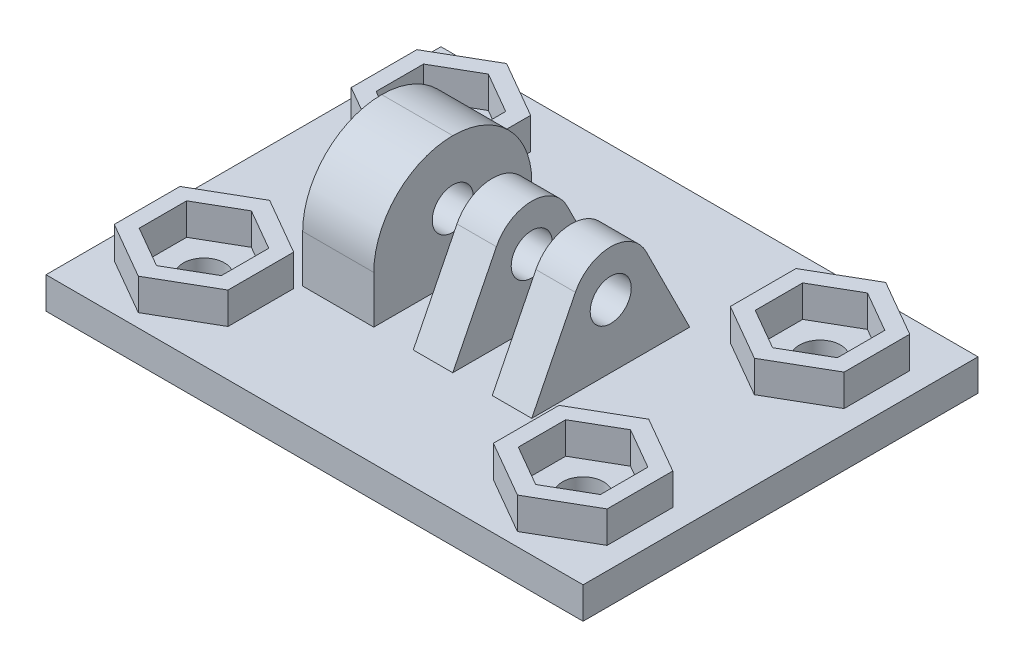
SolidWorks part; units mm, degrees
ref_plane "Front Plane" through (0, 0, 0) normal (0, 0, 1) x (1, 0, 0)
ref_plane "Top Plane" through (0, 0, 0) normal (0, 1, 0) x (1, 0, 0)
ref_plane "Right Plane" through (0, 0, 0) normal (1, 0, 0) x (0, 0, -1)
sketch "Sketch1" plane through (0, 0, 0) normal (0, 1, 0) x (1, 0, 0)
  line L0 (-21.59, 0) -> (-21.59, 31.75)
  line L1 (-21.59, 31.75) -> (21.59, 31.75)
  line L2 (-15.24, 25.4) -> (15.24, 25.4) construction
  line L3 (-15.24, 6.35) -> (15.24, 6.35) construction
  line L6 (21.59, 31.75) -> (21.59, 0)
  line L7 (21.59, 0) -> (-21.59, 0)
  line L8 (-15.24, 31.75) -> (-15.24, 0) construction
  line L9 (15.24, 31.75) -> (15.24, 0) construction
  circle A0 centre (-15.24, 25.4) radius 1.651
  circle A1 centre (-15.24, 6.35) radius 1.651
  circle A2 centre (15.24, 25.4) radius 1.651
  circle A3 centre (15.24, 6.35) radius 1.651
  dimension "D2" = 6.35
  dimension "D4" = 3.302
  dimension "D1" = 6.35
  dimension "D3" = 43.18
  dimension "D5" = 31.75
  dimension "D6" = 6.35
  dimension "D7" = 6.35
extrude "Boss-Extrude1" add sketch "Sketch1" along normal blind 2.54
sketch "Sketch2" plane through (0, 0, 0) normal (1, 0, 0) x (0, 0, -1)
  line L0 (22.225, 2.54) -> (15.875, 15.24)
  line L1 (0, 2.54) -> (31.75, 2.54) construction
  line L2 (15.875, 15.24) -> (9.525, 2.54)
  line L3 (22.225, 2.54) -> (9.525, 2.54)
  line L4 (15.875, 2.54) -> (15.875, 0) construction
  line L5 (0, 2.54) -> (31.75, 2.54) construction
  line L6 (0, 0) -> (31.75, 0) construction
  circle A0 centre (15.875, 7.62) radius 1.651
  dimension "D2" = 3.302
  dimension "D1" = 12.7
  dimension "D3" = 12.7
  dimension "D4" = 5.08
extrude "Boss-Extrude2" add sketch "Sketch2" along normal mid plane 15.875 contours L3 L0 L2 | A0
sketch "Sketch3" plane through (0, 2.54, 0) normal (0, 1, 0) x (1, 0, 0)
  line L1 (7.9375, 22.225) -> (-7.9375, 22.225) construction
  line L2 (-4.7625, 22.225) -> (-1.5875, 22.225)
  line L3 (-4.7625, 22.225) -> (-4.7625, 9.525)
  line L4 (-4.7625, 9.525) -> (-1.5875, 9.525)
  line L6 (-1.5875, 22.225) -> (-1.5875, 9.525)
  line L8 (7.9375, 9.525) -> (-7.9375, 9.525) construction
  line L9 (1.5875, 22.225) -> (4.7625, 22.225)
  line L10 (1.5875, 22.225) -> (1.5875, 9.525)
  line L11 (1.5875, 9.525) -> (4.7625, 9.525)
  line L12 (4.7625, 22.225) -> (4.7625, 9.525)
  line L13 (-1.5875, 9.525) -> (1.5875, 9.525) construction
  line L14 (0, 9.525) -> (0, 0) construction
  line L15 (-21.59, 0) -> (21.59, 0) construction
  dimension "D1" = 3.175
  dimension "D2" = 3.175
extrude "Cut-Extrude1" cut sketch "Sketch3" along normal up to vertex (12.7 mm away) up to point (7.9375, 15.24, -15.875)
fillet "Fillet1" radius 3.175 3 edges at (6.35, 15.24, -15.875) (0, 15.24, -15.875) (-6.35, 15.24, -15.875)
sketch "Sketch6" plane through (-7.9375, 0, 0) normal (-1, 0, 0) x (0, 0, 1)
  line L1 (-9.525, 2.54) -> (-22.225, 2.54)
  line L2 (-9.525, 2.54) -> (-9.525, 12.7)
  line L3 (-9.525, 12.7) -> (-22.225, 12.7)
  line L4 (-22.225, 2.54) -> (-22.225, 12.7)
  circle A0 centre (-15.875, 7.62) radius 1.651
  circle A1 centre (-15.875, 7.62) radius 1.651 construction
  dimension "D1" = 10.16
extrude "Boss-Extrude5" add sketch "Sketch6" against normal up to surface (3.175 mm away) up to face at (-4.7625, 7.62, -17.526)
sketch "Sketch4" plane through (-7.9375, 0, 0) normal (-1, 0, 0) x (0, 0, 1)
  line L0 (-22.225, 12.7) -> (-22.225, 2.54) construction
  line L1 (-22.225, 2.54) -> (-9.525, 2.54)
  line L2 (-22.225, 2.54) -> (-22.225, 12.7)
  line L3 (-22.225, 12.7) -> (-9.525, 12.7)
  line L4 (-9.525, 2.54) -> (-9.525, 12.7)
  line L5 (-15.875, 3.8072) -> (-12.573, 5.7136)
  line L6 (-12.573, 5.7136) -> (-12.573, 9.5264)
  line L7 (-12.573, 9.5264) -> (-15.875, 11.4328)
  line L8 (-15.875, 11.4328) -> (-19.177, 9.5264)
  line L9 (-19.177, 9.5264) -> (-19.177, 5.7136)
  line L10 (-19.177, 5.7136) -> (-15.875, 3.8072)
  line L11 (-22.225, 2.54) -> (-9.525, 2.54) construction
  circle A0 centre (-15.875, 7.62) radius 3.302 construction
  circle A1 centre (-15.875, 7.62) radius 1.651 construction
  circle A2 centre (-15.875, 7.62) radius 1.651
  point P5 (0, 0)
  point P8 (-22.225, 2.54)
  point P23 (0, 0)
  point P24 (0, 0)
  point P25 (-9.525, 2.54)
  line M7 (-22.225, 2.54) -> (-9.525, 2.54)
  line M24 (-9.525, 2.54) -> (-9.525, 12.7)
  line M25 (-9.525, 12.7) -> (-22.225, 12.7)
  line M26 (-22.225, 12.7) -> (-22.225, 2.54)
  dimension "D1" = 10.16
  dimension "D2" = 6.604
extrude "Boss-Extrude6" add sketch "Sketch4" along normal blind 2.54 contours L10 L9 L8 L7 L6 L5 M26 M7 M24 M25 region at (-7.9375, 7.62, -22.0624)
fillet "Fillet2" radius 6.35 2 edges at (-7.62, 12.7, -9.525) (-7.62, 12.7, -22.225)
sketch "Sketch7" plane through (0, 2.54, 0) normal (0, 1, 0) x (1, 0, 0)
  line L1 (-15.24, 30.6793) -> (-19.812, 28.0396)
  line L2 (-19.812, 28.0396) -> (-19.812, 22.7604)
  line L3 (-19.812, 22.7604) -> (-15.24, 20.1207)
  line L4 (-15.24, 20.1207) -> (-10.668, 22.7604)
  line L5 (-10.668, 22.7604) -> (-10.668, 28.0396)
  line L6 (-10.668, 28.0396) -> (-15.24, 30.6793)
  line L7 (15.24, 29.2128) -> (11.938, 27.3064)
  line L8 (11.938, 27.3064) -> (11.938, 23.4936)
  line L9 (11.938, 23.4936) -> (15.24, 21.5872)
  line L10 (15.24, 21.5872) -> (18.542, 23.4936)
  line L11 (18.542, 23.4936) -> (18.542, 27.3064)
  line L12 (18.542, 27.3064) -> (15.24, 29.2128)
  line L13 (15.24, 30.6793) -> (10.668, 28.0396)
  line L14 (10.668, 28.0396) -> (10.668, 22.7604)
  line L15 (10.668, 22.7604) -> (15.24, 20.1207)
  line L16 (15.24, 20.1207) -> (19.812, 22.7604)
  line L17 (-15.24, 29.2128) -> (-18.542, 27.3064)
  line L18 (-18.542, 27.3064) -> (-18.542, 23.4936)
  line L19 (-18.542, 23.4936) -> (-15.24, 21.5872)
  line L20 (-15.24, 21.5872) -> (-11.938, 23.4936)
  line L21 (-11.938, 23.4936) -> (-11.938, 27.3064)
  line L22 (-11.938, 27.3064) -> (-15.24, 29.2128)
  line L23 (19.812, 22.7604) -> (19.812, 28.0396)
  line L24 (19.812, 28.0396) -> (15.24, 30.6793)
  line L25 (15.24, 10.1628) -> (11.938, 8.2564)
  line L26 (11.938, 8.2564) -> (11.938, 4.4436)
  line L27 (11.938, 4.4436) -> (15.24, 2.5372)
  line L28 (15.24, 2.5372) -> (18.542, 4.4436)
  line L29 (18.542, 4.4436) -> (18.542, 8.2564)
  line L30 (18.542, 8.2564) -> (15.24, 10.1628)
  line L31 (15.24, 11.6293) -> (10.668, 8.9896)
  line L32 (10.668, 8.9896) -> (10.668, 3.7104)
  line L33 (10.668, 3.7104) -> (15.24, 1.0707)
  line L34 (15.24, 1.0707) -> (19.812, 3.7104)
  line L35 (19.812, 3.7104) -> (19.812, 8.9896)
  line L36 (19.812, 8.9896) -> (15.24, 11.6293)
  line L37 (-15.24, 10.1628) -> (-18.542, 8.2564)
  line L38 (-18.542, 8.2564) -> (-18.542, 4.4436)
  line L39 (-18.542, 4.4436) -> (-15.24, 2.5372)
  line L40 (-15.24, 2.5372) -> (-11.938, 4.4436)
  line L41 (-11.938, 4.4436) -> (-11.938, 8.2564)
  line L42 (-11.938, 8.2564) -> (-15.24, 10.1628)
  line L43 (-15.24, 11.6293) -> (-19.812, 8.9896)
  line L44 (-19.812, 8.9896) -> (-19.812, 3.7104)
  line L45 (-19.812, 3.7104) -> (-15.24, 1.0707)
  line L46 (-15.24, 1.0707) -> (-10.668, 3.7104)
  line L47 (-10.668, 3.7104) -> (-10.668, 8.9896)
  line L48 (-10.668, 8.9896) -> (-15.24, 11.6293)
  circle A0 centre (-15.24, 25.4) radius 3.302 construction
  circle A1 centre (-15.24, 25.4) radius 4.572 construction
  circle A2 centre (15.24, 25.4) radius 3.302 construction
  circle A3 centre (15.24, 25.4) radius 4.572 construction
  circle A4 centre (15.24, 6.35) radius 3.302 construction
  circle A5 centre (15.24, 6.35) radius 4.572 construction
  circle A6 centre (-15.24, 6.35) radius 3.302 construction
  circle A7 centre (-15.24, 6.35) radius 4.572 construction
  point P4 (0, 0)
  point P9 (0, 0)
  point P14 (15.24, 29.3595)
  point P19 (0, 0)
  point P53 (0, 0)
  point P69 (0, 0)
  point P70 (0, 0)
  point P71 (15.24, 8.6783)
  dimension "D1" = 6.604
  dimension "D2" = 1.27
extrude "Boss-Extrude7" add sketch "Sketch7" along normal blind 2.54
